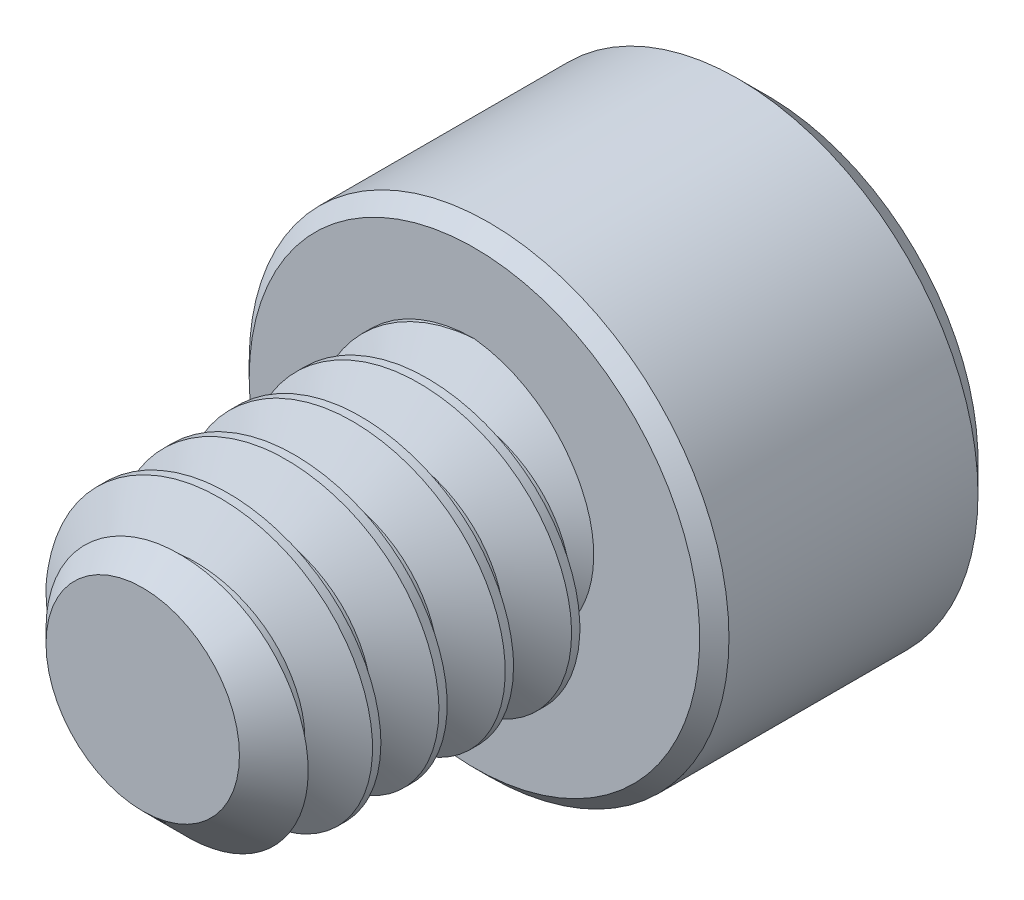
SolidWorks part; units mm, degrees
ref_plane "Front Plane" through (0, 0, 0) normal (0, 0, 1) x (1, 0, 0)
ref_plane "Top Plane" through (0, 0, 0) normal (0, 1, 0) x (1, 0, 0)
ref_plane "Right Plane" through (0, 0, 0) normal (1, 0, 0) x (0, 0, -1)
sketch "Sketch1" plane through (0, 0, 0) normal (0, 0, 1) x (1, 0, 0)
  line L0 (0, 1.7526) -> (0, -1.7526) construction
  circle A0 centre (0, 0) radius 1.7526
  dimension "OD" = 3.5052
extrude "Extrude1" add sketch "Sketch1" against normal blind 3.9688
sketch "Sketch2" plane through (0, 0, 0) normal (0, 0, 1) x (1, 0, 0)
  circle A0 centre (0, 0) radius 1.7526 construction
  circle A1 centre (0, 0) radius 1.7526
curve "Helix/Spiral1" pitch 0.7937 height 4.7625 turns 6 parameters "pitch"=0.7937
chamfer "Chamfer3" distance 0.5953 angle 45 1 edges at (1.7526, 0, 0)
sketch "Sketch3" plane through (0, 0, 0) normal (1, 0, 0) x (0, 0, -1)
  line L0 (-0.6945, 1.7526) -> (-0.3969, 1.237)
  line L1 (-0.3969, 1.237) -> (-0.2977, 1.237)
  line L2 (-0.2977, 1.237) -> (0, 1.7526)
  line L3 (-0.6945, 1.7526) -> (0, 1.7526)
  line L4 (-0.3473, 1.7526) -> (-0.3473, 1.237) construction
  line L5 (-0.5457, 1.4948) -> (-0.1488, 1.4948) construction
  line L6 (0, 1.7526) -> (0, -1.7526) construction
  dimension "D1" = 0.0992
  dimension "D2" = 0.3969
  dimension "D3" = 60
sweep "Cut-Sweep1" cut profiles "Sketch3" path "Helix/Spiral1"
sketch "Sketch6" plane through (0, 0, -3.9688) normal (0, 0, -1) x (-1, 0, 0)
  circle A0 centre (0, 0) radius 2.8702
  dimension "head dia" = 5.7404
extrude "Extrude2" add sketch "Sketch6" along normal blind 3.5052
sketch "Sketch7" plane through (0, 0, -7.474) normal (0, 0, -1) x (-1, 0, 0)
  line L1 (0, 1.604) -> (-1.3891, 0.802)
  line L2 (-1.3891, 0.802) -> (-1.3891, -0.802)
  line L3 (-1.3891, -0.802) -> (0, -1.604)
  line L4 (0, -1.604) -> (1.3891, -0.802)
  line L5 (1.3891, -0.802) -> (1.3891, 0.802)
  line L6 (1.3891, 0.802) -> (0, 1.604)
  circle A0 centre (0, 0) radius 1.3891 construction
  dimension "hex dia" = 2.7781
extrude "Cut-Extrude1" cut sketch "Sketch7" against normal blind 2.0836
sketch "Sketch8" plane through (0, 0, -7.474) normal (0, 0, -1) x (-1, 0, 0)
  circle A0 centre (0, 0) radius 1.604
extrude "Cut-Extrude2" cut sketch "Sketch8" against normal blind 0.3505 draft 45
chamfer "Chamfer1" distance 0.3505 angle 45 1 edges at (-2.8702, 0, -7.474)
chamfer "Chamfer2" distance 0.1753 angle 45 1 edges at (-2.8702, 0, -3.9688)
sketch "Sketch9" plane through (0, 0, 0) normal (1, 0, 0) x (0, 0, -1)
  line L0 (0, 1.7526) -> (0, -1.7526) construction
  line L1 (4.3656, 1.7526) -> (4.3656, -1.7526) construction
  line L2 (3.9688, 2.8702) -> (3.9688, -2.8702) construction
  line L3 (7.474, 2.8702) -> (7.474, -2.8702) construction
  line L4 (7.474, 0) -> (0, 0) construction
  dimension "D1" = 4.3656
  dimension "D2" = 3.5052
  dimension "D3" = 5.7404
  dimension "D4" = 3.9688
equation "\"D3@Helix/Spiral1\" = \"screw length@Extrude1\"+\"pitch@Helix/Spiral1\""
equation "\"D1@Sketch3\" = \"pitch@Helix/Spiral1\"*.125"
equation "\"D2@Sketch3\" = \"pitch@Helix/Spiral1\"*.5"
equation "\"D1@Cut-Extrude1\" = \"hex dia@Sketch7\"*.75"
equation "\"D1@Chamfer1\" = \"head depth@Extrude2\"/10"
equation "\"D1@Sketch9\" = \"pitch@Helix/Spiral1\"*5.5"
equation "\"D1@Chamfer2\" = \"D1@Chamfer1\"/2"
equation "\"D1@Cut-Extrude2\" = \"D1@Chamfer2\"*2"
equation "\"D1@Chamfer3\" = \"pitch@Helix/Spiral1\"*.750"
equation "\"D2@Sketch9\" = \"head depth@Extrude2\""
equation "\"D3@Sketch9\" = \"head dia@Sketch6\""
equation "\"D4@Sketch9\" = \"screw length@Extrude1\""
